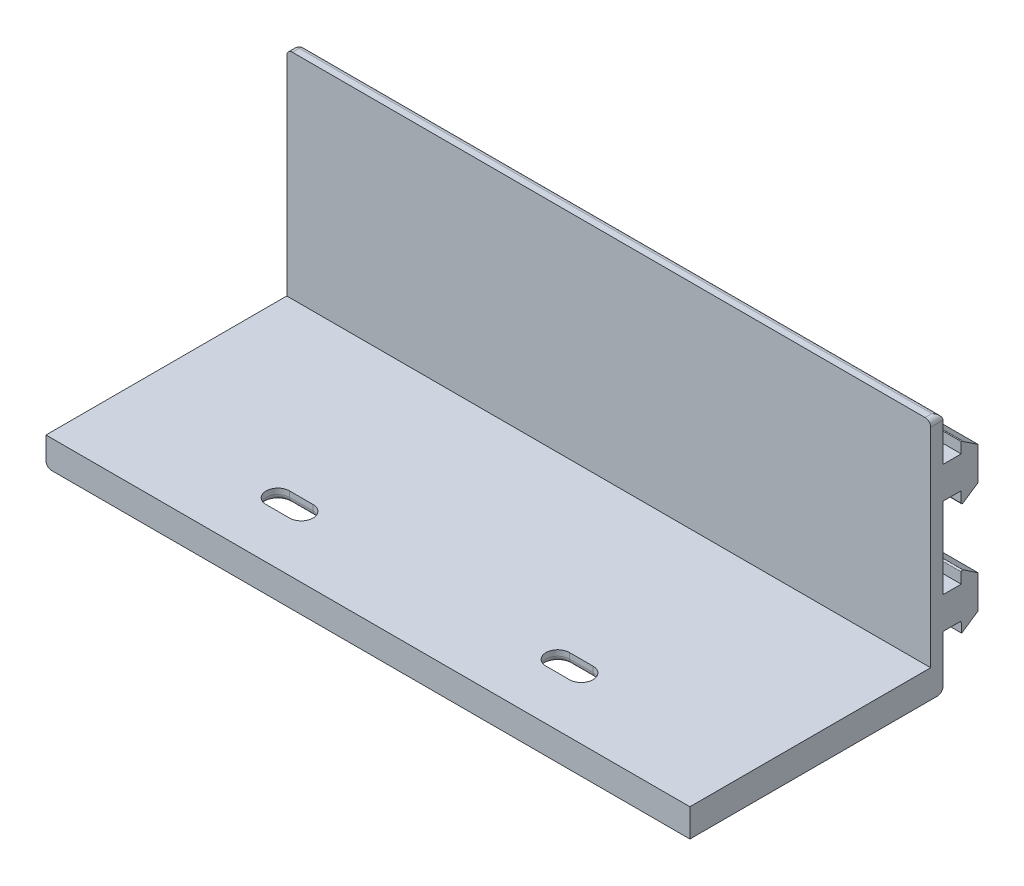
SolidWorks part; units mm, degrees
ref_plane "Спереди" through (0, 0, 0) normal (0, 0, 1) x (1, 0, 0)
ref_plane "Сверху" through (0, 0, 0) normal (0, 1, 0) x (1, 0, 0)
ref_plane "Справа" through (0, 0, 0) normal (1, 0, 0) x (0, 0, -1)
sketch "Эскиз1" plane through (0, 0, 0) normal (0, 1, 0) x (1, 0, 0)
  line L1 (0, 0) -> (115, 0)
  line L2 (0, 0) -> (0, 30)
  line L3 (0, 30) -> (115, 30)
  line L4 (115, 0) -> (115, 30)
  dimension "D1" = 30
  dimension "D2" = 115
extrude "Бобышка-Вытянуть1" add sketch "Эскиз1" along normal blind 29
shell "Оболочка1" thickness 2
sketch "Эскиз4" plane through (115, 0, 0) normal (1, 0, 0) x (0, 0, -1)
  line L0 (0, 0) -> (30, 0) construction
  line L1 (42.5, 0) -> (42.5, 63)
  line L2 (42.5, 63) -> (-12.5, 63)
  line L3 (-12.5, 63) -> (-12.5, 0)
  line L4 (-12.5, 0) -> (42.5, 0)
  point P8 (15, 0)
  point P9 (15, 0)
  dimension "D1" = 55
  dimension "D2" = 63
extrude "Бобышка-Вытянуть2" add sketch "Эскиз4" along normal blind 2
sketch "Эскиз7" plane through (117, 0, 0) normal (1, 0, 0) x (0, 0, -1)
  line L0 (-12.5, 0) -> (42.5, 0) construction
  line L1 (0, 7) -> (28, 7)
  line L2 (0, 7) -> (0, 56)
  line L3 (0, 56) -> (28, 56)
  line L4 (28, 7) -> (28, 56)
  line L5 (42.5, 0) -> (42.5, 63) construction
  dimension "D1" = 49
  dimension "D2" = 28
  dimension "D3" = 7
  dimension "D4" = 14.5
extrude "Вырез-Вытянуть2" cut sketch "Эскиз7" against normal blind 28
sketch "Эскиз8" plane through (117, 0, 0) normal (1, 0, 0) x (0, 0, -1)
  line L0 (-5.5, 31.5) -> (33.5, 31.5) construction
  line L2 (14, 56) -> (14, 7) construction
  line L4 (28, 56) -> (0, 56) construction
  line L6 (0, 7) -> (28, 7) construction
  circle A0 centre (-5.5, 31.5) radius 1.2
  point P6 (14, 31.5)
  dimension "D2" = 2.4
  dimension "D1" = 39
sketch "Эскиз10" plane through (0, 29, 0) normal (0, 1, 0) x (1, 0, 0)
  line L2 (115, 30) -> (0, 30) construction
  line L11 (115, 42.5) -> (115, -12.5) construction
  line L12 (115, 30) -> (115, 28)
  line L13 (87, 30) -> (115, 30)
  line L14 (89, 28) -> (115, 28)
  line L15 (89, 28) -> (2, 28)
  line L16 (0, 30) -> (0, 0) construction
  line L17 (0, 28) -> (0, 30)
  line L18 (0, 30) -> (87, 30)
  line L19 (0, 0) -> (0, 28)
  line L20 (2, 28) -> (2, 0)
  line L21 (0, 0) -> (89, 0) construction
  line L22 (2, 0) -> (0, 0)
  dimension "D1" = 2
extrude "Бобышка-Вытянуть6" add sketch "Эскиз10" along normal blind 29
sketch "Эскиз13" plane through (0, 0, 0) normal (0, -1, 0) x (1, 0, 0)
  line L0 (0, 0) -> (0, 40)
  line L1 (115, 12.5) -> (115, 40)
  line L2 (115, 40) -> (0, 40)
  line L3 (30.4, 35.95) -> (34.6, 35.95)
  line L4 (30.4, 31.75) -> (34.6, 31.75)
  line L5 (80.4, 35.95) -> (84.6, 35.95)
  line L6 (84.6, 31.75) -> (80.4, 31.75)
  line L7 (0, 0) -> (115, 0) construction
  arc A2 (30.4, 35.95) -> (30.4, 31.75) centre (30.4, 33.85) ccw
  arc A3 (84.6, 31.75) -> (84.6, 35.95) centre (84.6, 33.85) ccw
  arc A4 (80.4, 35.95) -> (80.4, 31.75) centre (80.4, 33.85) ccw
  arc A5 (34.6, 31.75) -> (34.6, 35.95) centre (34.6, 33.85) ccw
  line M18 (115, 12.5) -> (115, 0)
  line M19 (115, 0) -> (0, 0)
  dimension "D3" = 30.4
  dimension "D5" = 30.4
  dimension "D1" = 40
  dimension "D2" = 45.8
  dimension "D4" = 31.75
extrude "Бобышка-Вытянуть8" add sketch "Эскиз13" against normal blind 2 contours L1 L2 L0 A5 L4 A2 L3 A4 L5 A3 L6 M19 M18
sketch "Эскиз14" plane through (0, 0, 0) normal (-1, 0, 0) x (0, 0, 1)
  line L9 (-33.2548, 26.65) -> (-33.2548, 24.75)
  line L10 (-30, 26.65) -> (-33.2548, 26.65)
  line L11 (-30, 32.35) -> (-30, 26.65)
  line L12 (-33.2548, 32.35) -> (-30, 32.35)
  line L13 (-33.2548, 34.25) -> (-33.2548, 32.35)
  line L14 (-36.2548, 32.3263) -> (-33.5657, 34.119)
  line L15 (-36.2548, 26.3763) -> (-36.2548, 32.3263)
  line L16 (-33.5657, 24.5836) -> (-36.2548, 26.3763)
  line L17 (-33.2547, 6.5) -> (-33.303, 4.6006)
  line L18 (-30, 6.5) -> (-33.2547, 6.5)
  line L19 (-30, 12.2) -> (-30, 6.5)
  line L20 (-33.2548, 12.2) -> (-30, 12.2)
  line L21 (-33.2548, 14.1) -> (-33.2548, 12.2)
  line L22 (-36.2548, 12.4737) -> (-33.5657, 14.2664)
  line L23 (-36.2548, 6.5237) -> (-36.2548, 12.4737)
  line L24 (-33.5657, 4.731) -> (-36.2548, 6.5237)
  line L25 (-30, 58) -> (-30, 0) construction
  line L26 (-30, 0) -> (40, 0) construction
  arc A2 (-33.5657, 34.119) -> (-33.2548, 34.25) centre (-33.3686, 34.0855) cw
  arc A3 (-33.2548, 24.75) -> (-33.5657, 24.5836) centre (-33.4548, 24.75) cw
  arc A4 (-33.5657, 14.2664) -> (-33.2548, 14.1) centre (-33.4548, 14.1) cw
  arc A5 (-33.303, 4.6006) -> (-33.5657, 4.731) centre (-33.3739, 4.7876) cw
  dimension "D1" = 14.45
  dimension "D2" = 6.5
  dimension "D3" = 5.7
  dimension "D4" = 5.7
  dimension "D5" = 1.9
extrude "Бобышка-Вытянуть9" add sketch "Эскиз14" against normal up to surface (115 mm away) up to face at (115, 33.1818, -16)
fillet "Скругление1" radius 1 8 edges at (78.3, 0, 33.85) (82.5, 0, 31.75) (86.7, 0, 33.85) (28.3, 0, 33.85) (32.5, 0, 31.75) (36.7, 0, 33.85) (82.5, 0, 35.95) (32.5, 0, 35.95)
extrude "Вырез-Вытянуть5" cut sketch "Эскиз8" against normal blind 10
sketch "Эскиз15" plane through (0, 0, -28) normal (0, 0, 1) x (1, 0, 0)
  line L0 (2, 27) -> (2, 66.9795)
  line L1 (2, 27) -> (115, 27)
  line L2 (115, 63) -> (115, 2) construction
  line L3 (115, 27) -> (115, 66.9795)
  line L4 (115, 66.9795) -> (2, 66.9795)
extrude "Вырез-Вытянуть6" cut sketch "Эскиз15" along normal blind 33
sketch "Эскиз16" plane through (0, 0, -30) normal (0, 0, -1) x (-1, 0, 0)
  line L0 (-115, 0) -> (0, 0) construction
  line L1 (-45, 54.3) -> (-61.4, 54.3)
  line L2 (-45, 54.3) -> (-45, 45)
  line L3 (-45, 45) -> (-61.4, 45)
  line L4 (-61.4, 54.3) -> (-61.4, 45)
  line L5 (0, 58) -> (0, 32.35) construction
  dimension "D1" = 45
  dimension "D2" = 9.3
  dimension "D3" = 16.4
  dimension "D4" = 45
extrude "Вырез-Вытянуть7" cut sketch "Эскиз16" against normal up to surface (2 mm away)
sketch "Эскиз17" plane through (115, 0, 0) normal (-1, 0, 0) x (0, 0, 1)
  line L0 (-28, 58) -> (12.5, 58)
  line L1 (12.5, 58) -> (12.5, 56)
  line L2 (12.5, 56) -> (-28, 56)
  line L3 (-28, 56) -> (-28, 58)
  line L4 (12.5, 63) -> (12.5, 2) construction
extrude "Бобышка-Вытянуть10" add sketch "Эскиз17" along normal up to surface (113 mm away)
sketch "Эскиз20" plane through (0, 0, 0) normal (-1, 0, 0) x (0, 0, 1)
  line L0 (0, 2) -> (-27.8, 2)
  line L1 (-27.8, 2) -> (-27.8, 71.9653)
  line L2 (-27.8, 71.9653) -> (29.1595, 71.9653)
  line L3 (29.1595, 71.9653) -> (29.1595, 2)
  line L4 (0, 2) -> (40, 2) construction
  line L5 (29.1595, 2) -> (0, 2)
  line L7 (-30, 26.65) -> (-30, 12.2) construction
  dimension "D1" = 2.2
extrude "Вырез-Вытянуть8" cut sketch "Эскиз20" against normal blind 147
sketch "Эскиз21" plane through (0, 2, 0) normal (0, 1, 0) x (1, 0, 0)
  line L0 (115, -12.5) -> (115, 44.8007)
  line L1 (115, 44.8007) -> (135.1762, 44.8007)
  line L2 (135.1762, 44.8007) -> (135.1762, -12.5)
  line L3 (135.1762, -12.5) -> (115, -12.5)
extrude "Вырез-Вытянуть9" cut sketch "Эскиз21" against normal blind 147 and the other way blind 147
sketch "Эскиз22" plane through (0, 0, -28) normal (0, 0, 1) x (1, 0, 0)
  line L0 (113, 7) -> (115, 7)
  line L1 (115, 7) -> (115, 2)
  line L2 (115, 2) -> (113, 2)
  line L3 (113, 2) -> (113, 7)
  line L4 (115, 2) -> (0, 2) construction
extrude "Вырез-Вытянуть11" cut sketch "Эскиз22" along normal up to surface (0.2 mm away) up to face at (114, 4.5, -27.8)
sketch "Эскиз24" plane through (0, 0, -27.8) normal (0, 0, 1) x (1, 0, 0)
  line L0 (2, 56) -> (115, 56)
  line L1 (115, 56) -> (115, 0)
  line L2 (115, 0) -> (2, 0)
  line L3 (2, 0) -> (2, 56)
extrude "Бобышка-Вытянуть16" add sketch "Эскиз24" against normal up to surface (0.2 mm away)
sketch "Эскиз25" plane through (115, 0, 0) normal (1, 0, 0) x (0, 0, -1)
  line L0 (-61.3565, 61.7211) -> (45.2588, 61.7211)
  line L1 (45.2588, 61.7211) -> (45.2588, 40.2)
  line L2 (45.2588, 40.2) -> (-10.2, 40.2)
  line L3 (-61.3565, 40.2) -> (-61.3565, 61.7211)
  line L4 (30, 0) -> (-40, 0) construction
  line L5 (-10.2, 40.2) -> (-10.2, -7.9899)
  line L6 (-10.2, -7.9899) -> (-61.3565, -7.9899)
  line L7 (-61.3565, -7.9899) -> (-61.3565, 40.2)
  line L8 (27.8, 58) -> (27.8, 2) construction
  dimension "D1" = 40.2
  dimension "D2" = 38
extrude "Вырез-Вытянуть12" cut sketch "Эскиз25" against normal blind 147
sketch "Эскиз26" plane through (0, 2, 0) normal (0, 1, 0) x (1, 0, 0)
  line L0 (30.4, -2.1) -> (34.6, -2.1)
  line L1 (30.4, -6.3) -> (34.6, -6.3)
  line L2 (80.4, -2.1) -> (84.6, -2.1)
  line L3 (84.6, -6.3) -> (80.4, -6.3)
  line L4 (115, 27.8) -> (115, -10.2) construction
  line L5 (0, 27.8) -> (0, -10.2) construction
  line L7 (115, 27.8) -> (0, 27.8) construction
  arc A1 (34.6, -6.3) -> (34.6, -2.1) centre (34.6, -4.2) ccw
  arc A2 (30.4, -2.1) -> (30.4, -6.3) centre (30.4, -4.2) ccw
  arc A4 (80.4, -2.1) -> (80.4, -6.3) centre (80.4, -4.2) ccw
  arc A5 (84.6, -6.3) -> (84.6, -2.1) centre (84.6, -4.2) ccw
  dimension "D4" = 32
  dimension "D1" = 45.8
  dimension "D2" = 30.4
  dimension "D3" = 30.4
extrude "Вырез-Вытянуть13" cut sketch "Эскиз26" against normal blind 5
fillet "Скругление8" radius 1 9 edges at (0, 3.25, -30) (0, 19.425, -30) (0, 36.275, -30) (0, 40.2, -28.9) (57.5, 40.2, -30) (115, 40.2, -28.9) (57.5, 0, 10.2) (57.5, 0, -30) (0, 0, -9.9)
sketch "Эскиз27" plane through (0, 0, 0) normal (0, -1, 0) x (1, 0, 0)
  line L0 (115, -30) -> (115, -29) construction
  line L1 (115, 9.2) -> (115, 10.2) construction
  line L2 (115, -29) -> (115, 9.2) construction
  line L4 (0, -29) -> (0, 10.2) construction
  line L5 (115, -30) -> (1, -30) construction
  line L6 (115, -30) -> (115, -29)
  line L7 (115, 9.2) -> (115, 10.2)
  line L8 (115, -29) -> (115, 9.2)
  line L10 (0, -29) -> (0, 10.2)
  line L11 (115, -30) -> (1, -30)
  line L12 (84.6, 6.3) -> (80.4, 6.3) construction
  line L13 (80.4, 2.1) -> (84.6, 2.1) construction
  line L14 (30.4, 2.1) -> (34.6, 2.1) construction
  line L15 (34.6, 6.3) -> (30.4, 6.3) construction
  line L16 (84.6, 6.3) -> (80.4, 6.3)
  line L17 (80.4, 2.1) -> (84.6, 2.1)
  line L18 (30.4, 2.1) -> (34.6, 2.1)
  line L19 (34.6, 6.3) -> (30.4, 6.3)
  line L20 (0, 10.2) -> (0, 15.2)
  line L21 (0, 15.2) -> (115, 15.2)
  line L22 (115, 15.2) -> (115, 10.2)
  arc A0 (0, -29) -> (1, -30) centre (1, -29) ccw construction
  arc A1 (0, -29) -> (1, -30) centre (1, -29) ccw
  arc A2 (84.6, 2.1) -> (84.6, 6.3) centre (84.6, 4.2) ccw construction
  arc A3 (80.4, 6.3) -> (80.4, 2.1) centre (80.4, 4.2) ccw construction
  arc A4 (30.4, 6.3) -> (30.4, 2.1) centre (30.4, 4.2) ccw construction
  arc A5 (34.6, 2.1) -> (34.6, 6.3) centre (34.6, 4.2) ccw construction
  arc A6 (84.6, 2.1) -> (84.6, 6.3) centre (84.6, 4.2) ccw
  arc A7 (80.4, 6.3) -> (80.4, 2.1) centre (80.4, 4.2) ccw
  arc A8 (30.4, 6.3) -> (30.4, 2.1) centre (30.4, 4.2) ccw
  arc A9 (34.6, 2.1) -> (34.6, 6.3) centre (34.6, 4.2) ccw
  dimension "D1" = 5
extrude "Бобышка-Вытянуть17" add sketch "Эскиз27" along normal blind 3 and the other way blind 1
fillet "Скругление10" radius 1 3 edges at (58, -3, -30) (0.2929, -3, -29.7071) (0, -3, -6.9)
sketch "Эскиз28" plane through (0, 1, 0) normal (0, 1, 0) x (1, 0, 0)
  line L4 (115, -10.2) -> (0, -10.2)
  line L5 (0, -10.2) -> (0, -15.2)
  line L6 (0, -15.2) -> (115, -15.2)
  line L7 (115, -15.2) -> (115, -10.2)
  line L8 (115, -10.2) -> (0, -10.2)
  line L9 (0, -10.2) -> (0, -15.2)
  line L10 (0, -15.2) -> (115, -15.2)
  line L11 (115, -15.2) -> (115, -10.2)
  dimension "D1" = 0
extrude "Бобышка-Вытянуть18" add sketch "Эскиз28" along normal up to surface (1 mm away)
sketch "Эскиз29" plane through (0, -3, 0) normal (0, -1, 0) x (1, 0, 0)
  line L0 (80.4, 2.1) -> (84.6, 2.1) construction
  line L1 (84.6, 6.3) -> (80.4, 6.3) construction
  line L2 (30.4, 2.1) -> (34.6, 2.1) construction
  line L3 (34.6, 6.3) -> (30.4, 6.3) construction
  line L4 (80.4, 2.1) -> (84.6, 2.1)
  line L5 (84.6, 6.3) -> (80.4, 6.3)
  line L6 (30.4, 2.1) -> (34.6, 2.1)
  line L7 (34.6, 6.3) -> (30.4, 6.3)
  line L8 (30.4, 9.3) -> (34.6, 9.3)
  line L9 (30.4, -0.9) -> (34.6, -0.9)
  line L10 (80.4, -0.9) -> (84.6, -0.9)
  line L11 (84.6, 9.3) -> (80.4, 9.3)
  arc A0 (34.6, -0.9) -> (34.6, 9.3) centre (34.6, 4.2) ccw
  arc A1 (80.4, 9.3) -> (80.4, -0.9) centre (80.4, 4.2) ccw
  arc A2 (84.6, -0.9) -> (84.6, 9.3) centre (84.6, 4.2) ccw
  arc A3 (30.4, 9.3) -> (30.4, -0.9) centre (30.4, 4.2) ccw
  arc A4 (84.6, 2.1) -> (84.6, 6.3) centre (84.6, 4.2) ccw construction
  arc A5 (80.4, 6.3) -> (80.4, 2.1) centre (80.4, 4.2) ccw construction
  arc A6 (34.6, 2.1) -> (34.6, 6.3) centre (34.6, 4.2) ccw construction
  arc A7 (30.4, 6.3) -> (30.4, 2.1) centre (30.4, 4.2) ccw construction
  arc A8 (84.6, 2.1) -> (84.6, 6.3) centre (84.6, 4.2) ccw
  arc A9 (80.4, 6.3) -> (80.4, 2.1) centre (80.4, 4.2) ccw
  arc A10 (34.6, 2.1) -> (34.6, 6.3) centre (34.6, 4.2) ccw
  arc A11 (30.4, 6.3) -> (30.4, 2.1) centre (30.4, 4.2) ccw
  dimension "D1" = 3
extrude "Вырез-Вытянуть14" cut sketch "Эскиз29" against normal blind 3
chamfer "Фаска7" distance 3 angle 45 8 edges at (82.5, -3, -0.9) (89.7, -3, 4.2) (75.3, -3, 4.2) (82.5, -3, 9.3) (32.5, -3, -0.9) (39.7, -3, 4.2) (25.3, -3, 4.2) (32.5, -3, 9.3)
fillet "Скругление11" radius 1 8 edges at (36.7, 0, 4.2) (32.5, 0, 2.1) (28.3, 0, 4.2) (86.7, 0, 4.2) (82.5, 0, 2.1) (78.3, 0, 4.2) (32.5, 0, 6.3) (82.5, 0, 6.3)
chamfer "Фаска1" [suppressed] distance 1 angle 45
chamfer "Фаска2" [suppressed] distance 2 angle 45
fillet "Скругление2" [suppressed] radius 1
fillet "Скругление3" [suppressed] radius 1
sketch "Эскиз18" plane through (0, 2, 0) normal (0, 1, 0) x (1, 0, 0)
  line L0 (0, 0) -> (2, 0)
  line L1 (2, 0) -> (2, -1.7)
  line L3 (2, -1.7) -> (0, -1.7)
  line L4 (0, 27.8) -> (0, -15.2) construction
  line L5 (0, -1.7) -> (0, 0)
  dimension "D1" = 1.7
extrude "Бобышка-Вытянуть11" [suppressed] add sketch "Эскиз18" along normal up to surface (56 mm away)
sketch "Эскиз19" [suppressed] plane through (0, 58, 0) normal (0, 1, 0) x (1, 0, 0)
  line L0 (0, -1.7) -> (2, -1.7)
  line L1 (2, -1.7) -> (2, -12.5)
  line L4 (116, -14.5) -> (0, -14.5)
  line L5 (0, -14.5) -> (0, -1.7)
  line L6 (0, 27.8) -> (0, -15.2) construction
  line L7 (2, -12.5) -> (116, -12.5)
  line L8 (116, -12.5) -> (116, -14.5)
  dimension "D1" = 2
extrude "Бобышка-Вытянуть15" [suppressed] add sketch "Эскиз19" against normal blind 31
fillet "Скругление4" [suppressed] radius 1
fillet "Скругление5" [suppressed] radius 1
chamfer "Фаска3" [suppressed] distance 2 angle 45
chamfer "Фаска5" [suppressed] distance 1 angle 45
fillet "Скругление6" [suppressed] radius 1
chamfer "Фаска6" [suppressed] distance 1 angle 45
